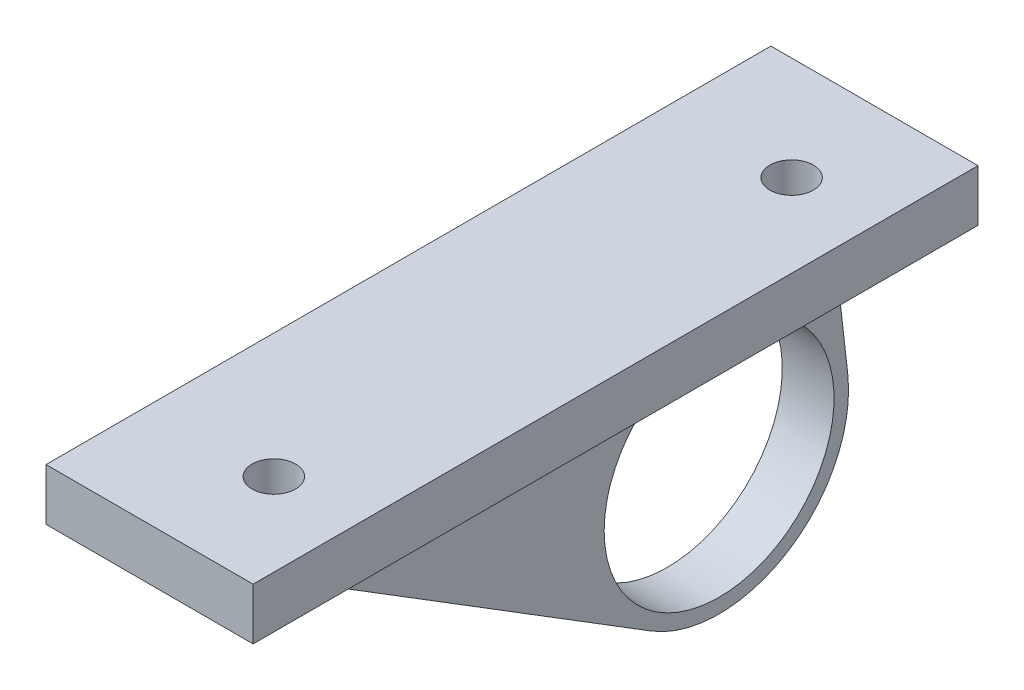
SolidWorks part; units mm, degrees
ref_plane "前基準面" through (0, 0, 0) normal (0, 0, 1) x (1, 0, 0)
ref_plane "上基準面" through (0, 0, 0) normal (0, 1, 0) x (1, 0, 0)
ref_plane "右基準面" through (0, 0, 0) normal (1, 0, 0) x (0, 0, -1)
sketch "草圖1" plane through (0, 0, 0) normal (0, 1, 0) x (1, 0, 0)
  line L1 (-10000, 35000) -> (10000, 35000)
  line L2 (-10000, 35000) -> (-10000, -35000)
  line L3 (-10000, -35000) -> (10000, -35000)
  line L4 (10000, 35000) -> (10000, -35000)
  line L5 (-10000, 35000) -> (10000, -35000) construction
  line L6 (-10000, -35000) -> (10000, 35000) construction
  circle A0 centre (2000, 25000) radius 2100
  circle A1 centre (2000, -25000) radius 2100
  point P0 (0, 0)
  dimension "D1" = 4200
  dimension "D3" = 10000
  dimension "D5" = 4200
  dimension "D6" = 10000
  dimension "D7" = 12000
  dimension "D8" = 12000
  dimension "D2" = 70000
  dimension "D4" = 20000
extrude "填料-伸長1" add sketch "草圖1" along normal blind 5000
sketch "草圖2" plane through (-10000, 0, 0) normal (-1, 0, 0) x (0, 0, 1)
  line L1 (-35000, 5000) -> (-35000, 0) construction
  line L2 (-37195.122, 24756.0976) -> (-37500, 27500)
  line L3 (-35000, 0) -> (-37418.4964, -21074.8873)
  line L4 (-35000, 5000) -> (35000, 5000)
  line L6 (35000, 0) -> (-18412.1672, -33123.1097)
  line L7 (35000, 0) -> (-35000, 0)
  arc A0 (-37500, 27500) -> (-37195.122, 24756.0976) centre (-25000, 27500) ccw
  circle A2 centre (-25000, -22500) radius 12500
  circle A3 centre (-25000, -22500) radius 11100
  line M1 (-35000, 0) -> (35000, 0)
  dimension "D5" = 22200
  dimension "D6" = 25000
  dimension "D8" = 10000
  dimension "D7" = 27500
extrude "填料-伸長4" add sketch "草圖2" against normal blind 5000 contours A0 L2 region at (-10000, 26124.6708, -37377.9632)
extrude "填料-伸長5" add sketch "草圖2<7>" against normal blind 5000 contours A2 L6 L3 M1 | A2 A3 region at (-10000, -10295.479, -6627.0273)
sketch "草圖2<7>" plane through (-10000, 0, 0) normal (-1, 0, 0) x (0, 0, 1) same geometry as "草圖2"
sketch "草圖3" plane through (-10000, 0, 0) normal (-1, 0, 0) x (0, 0, 1)
  line L0 (-35000, 5000) -> (35000, 5000) construction
  line L1 (-22515.2176, 5000) -> (-40149.7883, 5000)
  line L2 (-22515.2176, 5000) -> (-22515.2176, 27931.7164)
  line L3 (-22515.2176, 27931.7164) -> (-40149.7883, 27931.7164)
  line L4 (-40149.7883, 5000) -> (-40149.7883, 27931.7164)
extrude "除料-伸長1" cut sketch "草圖3" against normal blind 24449
